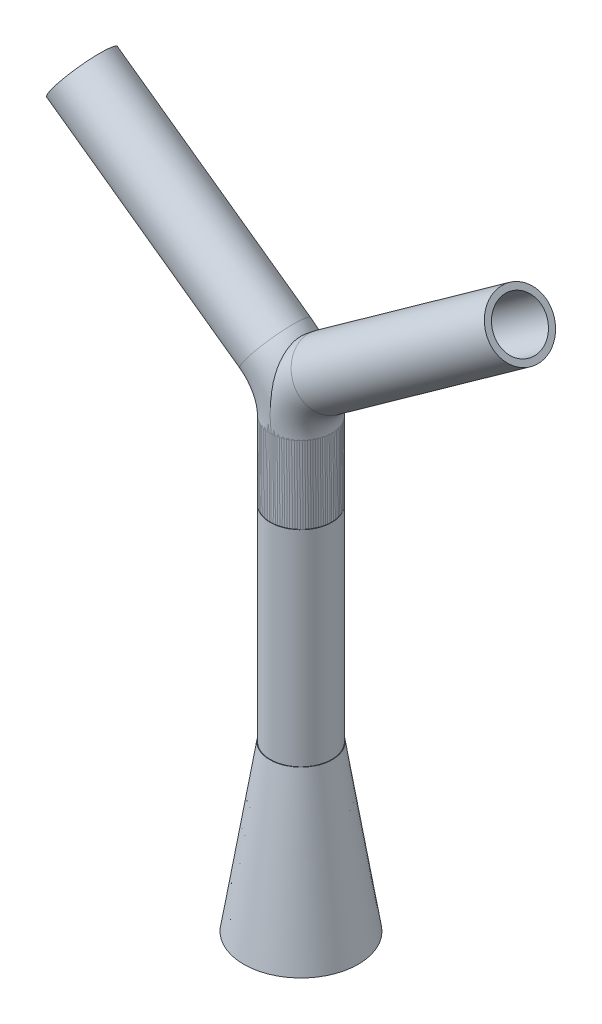
SolidWorks part; units mm, degrees
ref_plane "Plano frontal" through (0, 0, 0) normal (0, 0, 1) x (1, 0, 0)
ref_plane "Plano superior" through (0, 0, 0) normal (0, 1, 0) x (1, 0, 0)
ref_plane "Plano direito" through (0, 0, 0) normal (1, 0, 0) x (0, 0, -1)
sketch3d "3DSketch1"
  line L0 (-22872.6177, -6028.9657, 40486.7002) -> (-22872.6177, -6100.4657, 40486.7002) construction
  line L1 (-22872.6177, -6028.9657, 40486.7002) -> (-22872.6177, -5933.0872, 40486.7002) construction
  circle A0 centre (-22872.6177, -6028.9657, 40486.7002) radius 27.9
  circle A1 centre (-22872.6177, -6028.9657, 40486.7002) radius 26.3
  circle A2 centre (-22872.6177, -5933.0872, 40486.7002) radius 15
  circle A3 centre (-22872.6177, -5933.0872, 40486.7002) radius 12
  point P2 (-22872.6177, -6001.0657, 40486.7002)
  point P6 (-22872.6177, -6002.6657, 40486.7002)
  point P10 (-22872.6177, -5918.0872, 40486.7002)
  point P11 (-22872.6177, -5921.0872, 40486.7002)
  dimension "D1" = 30
  dimension "D2" = 3
sketch "Sketch1" plane through (0, -6028.9657, 0) normal (0, 1, 0) x (1, 0, 0)
  circle A0 centre (-22872.6177, -40486.7002) radius 27.9
  circle A1 centre (-22872.6177, -40486.7002) radius 26.3
  circle M2 centre (-22872.6177, -40486.7002) radius 27.9
  circle M3 centre (-22872.6177, -40486.7002) radius 26.3
extrude "Boss-Extrude1" add sketch "Sketch1" along normal blind 80 draft 9 contours M3 | M2 M3 region at (-22899.7286, -6028.9657, 40486.7002) region at (-22872.6177, -6028.9657, 40486.7002)
sketch "Sketch2" plane through (0, -5948.9657, 0) normal (0, 1, 0) x (1, 0, 0)
  circle A0 centre (-22872.6177, -40486.7002) radius 12
extrude "Cut-Extrude1" cut sketch "Sketch2" against normal blind 80 draft 9 draft outward yes
sketch3d "3DSketch2"
  line L0 (-22872.6177, -5948.9657, 40486.7002) -> (-22872.6177, -5848.9657, 40486.7002)
  line L1 (-22872.6177, -6028.9657, 40486.7002) -> (-22872.6177, -5948.9657, 40486.7002) construction
  line L2 (-22872.6177, -6028.9657, 40486.7002) -> (-22872.6177, -5933.0872, 40486.7002) construction
sweep "Sweep-Thin1" add path "3DSketch2" circular profile diameter 30 parameters "D1"=3, "D3"=30
sketch3d "3DSketch3"
  line L0 (-22885.1679, -5786.9602, 40486.7002) -> (-22979.2971, -5719.6517, 40486.7002)
  line L2 (-22872.6177, -5848.7854, 40486.7002) -> (-22872.6177, -5811.3632, 40486.7002)
  line L4 (-22872.6177, -5795.9345, 40486.7002) -> (-22909.3454, -5795.9345, 40486.7002) construction
  line L5 (-22909.3454, -5795.9345, 40486.7002) -> (-22909.3454, -5769.6717, 40486.7002) construction
  line L6 (-22872.6177, -5848.9657, 40486.7002) -> (-22872.6177, -5848.7854, 40486.7002) construction
  line L7 (-22872.6177, -5948.9657, 40486.7002) -> (-22872.6177, -5848.9657, 40486.7002) construction
  arc A0 (-22872.6177, -5811.3632, 40486.7002) -> (-22885.1679, -5786.9602, 40486.7002) centre (-22902.6177, -5811.3632, 40486.7002) ccw
  point P11 (-22872.6177, -5795.9345, 40486.7002)
  point P13 (-22902.6177, -5811.3632, 40516.7002)
  dimension "D1" = 30
sweep "Sweep-Thin3" add path "3DSketch3" circular profile diameter 30 parameters "D1"=3, "D3"=30
pattern_circular "CirPattern1" count 2 every 180 about axis through (-22872.6177, -5848.9657, 40486.7002) along (0, 1, 0) of bodies 106
